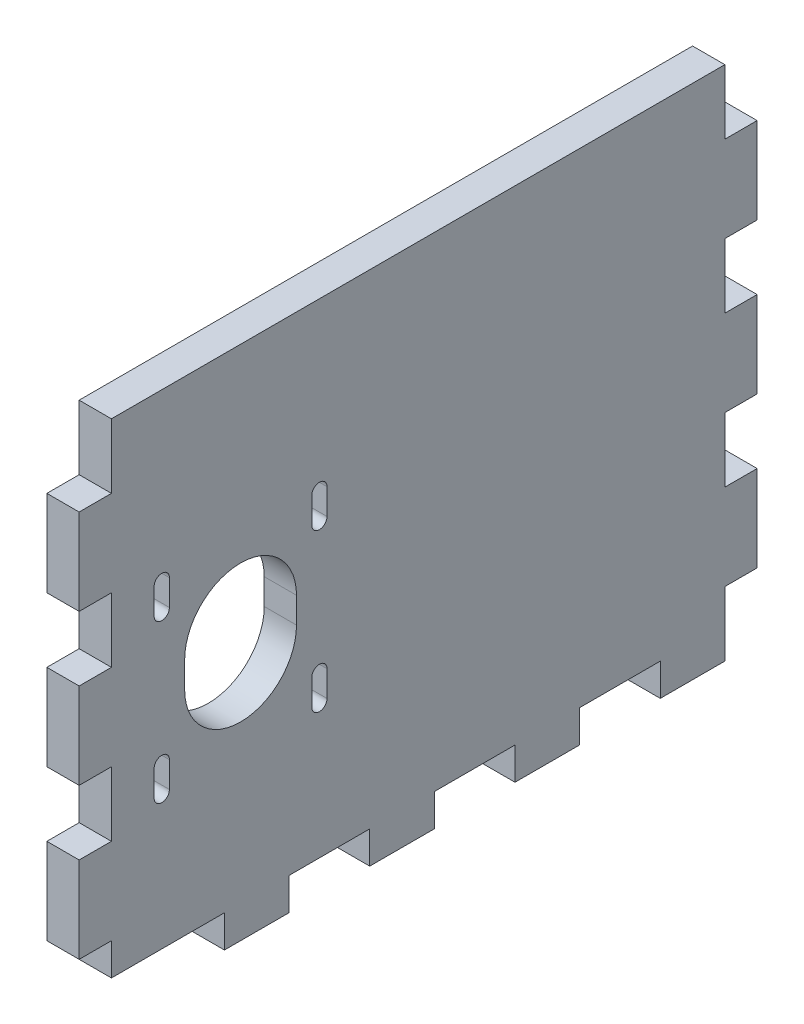
SolidWorks part; units mm, degrees
material "Acrylic (Medium-high impact)"
ref_plane "Front" through (0, 0, 0) normal (0, 0, 1) x (1, 0, 0)
ref_plane "Top" through (0, 0, 0) normal (0, 1, 0) x (1, 0, 0)
ref_plane "Right" through (0, 0, 0) normal (1, 0, 0) x (0, 0, -1)
sketch "Sketch1" plane through (0, 0, 0) normal (0, 0, 1) x (1, 0, 0)
  line L0 (0, 143.002) -> (0, -143.002) construction
  line L1 (-3.302, 133.858) -> (-3.302, -143.002)
  line L2 (-3.302, -143.002) -> (3.302, -143.002)
  line L3 (3.302, 143.002) -> (3.302, -143.002)
  line L4 (3.302, 143.002) -> (-16.256, 143.002)
  line L5 (-5.842, 136.398) -> (-16.256, 136.398)
  line L6 (-16.256, 143.002) -> (-16.256, 136.398)
  line L8 (-28.956, 155.448) -> (16.002, 155.448)
  line L9 (-28.956, 155.448) -> (-28.956, -149.352)
  line L10 (-28.956, -149.352) -> (16.002, -149.352)
  line L11 (16.002, 155.448) -> (16.002, -149.352)
  arc A0 (-3.302, 133.858) -> (-5.842, 136.398) centre (-5.842, 133.858) ccw
  point P2 (0, -143.002)
  point P11 (0, 0)
  dimension "D5" = 2.54
  dimension "D1" = 6.604
  dimension "D2" = 12.954
  dimension "D3" = 6.604
  dimension "D4" = 286.004
  dimension "D6" = 304.8
  dimension "D7" = 6.35
  dimension "D8" = 12.7
  dimension "D9" = 12.7
extrude "Boss-Extrude1" add sketch "Sketch1" along normal blind 6.35
sketch "Sketch2" plane through (16.002, 0, 0) normal (1, 0, 0) x (0, 0, -1)
  line L0 (-6.35, -149.352) -> (-6.35, 155.448) construction
  line L1 (-6.35, -47.752) -> (127, -47.752)
  line L2 (-6.35, -47.752) -> (-6.35, -149.352)
  line L3 (-6.35, -149.352) -> (127, -149.352)
  line L4 (127, -47.752) -> (127, -149.352)
  line L5 (14.4, -101.092) -> (14.4, -96.012)
  line L6 (36.4, -96.012) -> (36.4, -101.092)
  line L7 (8.4, -116.592) -> (8.4, -111.512)
  line L8 (11.4, -116.592) -> (11.4, -111.512)
  line L9 (8.4, -85.592) -> (8.4, -80.512)
  line L10 (11.4, -85.592) -> (11.4, -80.512)
  line L11 (25.4, -96.012) -> (25.4, -101.092) construction
  line L12 (42.4, -116.592) -> (42.4, -111.512)
  line L13 (39.4, -116.592) -> (39.4, -111.512)
  line L14 (39.4, -85.592) -> (39.4, -80.512)
  line L15 (42.4, -85.592) -> (42.4, -80.512)
  line L16 (0, -149.352) -> (0, 155.448) construction
  line L17 (123.825, -60.452) -> (123.825, -77.3853) construction
  line L18 (127, -47.752) -> (120.65, -47.752)
  line L19 (127, -47.752) -> (127, -60.452)
  line L20 (127, -60.452) -> (120.65, -60.452)
  line L21 (120.65, -47.752) -> (120.65, -60.452)
  line L22 (127, -107.0187) -> (120.65, -107.0187)
  line L23 (127, -107.0187) -> (127, -119.7187)
  line L24 (127, -119.7187) -> (120.65, -119.7187)
  line L25 (120.65, -107.0187) -> (120.65, -119.7187)
  line L26 (127, -136.652) -> (120.65, -136.652)
  line L27 (127, -136.652) -> (127, -149.352)
  line L28 (127, -149.352) -> (120.65, -149.352)
  line L29 (120.65, -136.652) -> (120.65, -149.352)
  line L30 (127, -77.3853) -> (120.65, -77.3853)
  line L31 (127, -77.3853) -> (127, -90.0853)
  line L32 (127, -90.0853) -> (120.65, -90.0853)
  line L33 (120.65, -77.3853) -> (120.65, -90.0853)
  line L34 (123.825, -90.0853) -> (123.825, -107.0187) construction
  line L35 (123.825, -119.7187) -> (123.825, -136.652) construction
  arc A0 (14.4, -101.092) -> (36.4, -101.092) centre (25.4, -101.092) ccw
  arc A1 (36.4, -96.012) -> (14.4, -96.012) centre (25.4, -96.012) ccw
  arc A2 (8.4, -116.592) -> (11.4, -116.592) centre (9.9, -116.592) ccw
  arc A3 (11.4, -111.512) -> (8.4, -111.512) centre (9.9, -111.512) ccw
  arc A4 (8.4, -85.592) -> (11.4, -85.592) centre (9.9, -85.592) ccw
  arc A5 (11.4, -80.512) -> (8.4, -80.512) centre (9.9, -80.512) ccw
  arc A6 (42.4, -116.592) -> (39.4, -116.592) centre (40.9, -116.592) cw
  arc A7 (39.4, -111.512) -> (42.4, -111.512) centre (40.9, -111.512) cw
  arc A8 (42.4, -85.592) -> (39.4, -85.592) centre (40.9, -85.592) cw
  arc A9 (39.4, -80.512) -> (42.4, -80.512) centre (40.9, -80.512) cw
  point P44 (25.4, -98.552)
  point P47 (-6.35, -98.552)
  line M17 (0, -149.352) -> (0, 155.448)
  line M19 (-6.35, 155.448) -> (-6.35, -149.352)
  line M20 (-6.35, -149.352) -> (0, -149.352)
  dimension "D1" = 22
  dimension "D6" = 1.5
  dimension "D10" = 1.5
  dimension "D2" = 5.08
  dimension "D3" = 5.08
  dimension "D4" = 15.5
  dimension "D5" = 15.5
  dimension "D7" = 15.5
  dimension "D8" = 15.5
  dimension "D9" = 5.08
  dimension "D11" = 25.4
  dimension "D12" = 50.8
  dimension "D13" = 101.6
  dimension "D14" = 12.7
  dimension "D15" = 6.35
extrude "Boss-Extrude2" add sketch "Sketch2" against normal blind 6.35 contours L33 L30 L4 L20 L21 L1 L3 L29 L26 L24 L25 L22 L32 A5 L10 A4 L9 A3 L8 A2 L7 A1 L6 A0 L5 L13 A7 L12 A6 L14 A9 L15 A8 M17 | L1 M19 M20 M17 region at (16.002, -98.552, -63.7235) region at (16.002, -98.552, 3.175)
sketch "Sketch3" plane through (9.652, 0, 0) normal (-1, 0, 0) x (0, 0, 1)
  line L0 (-120.65, -136.652) -> (-120.65, -149.352) construction
  line L1 (-120.65, -143.002) -> (0, -143.002)
  line L2 (-120.65, -143.002) -> (-120.65, -149.352)
  line L3 (-120.65, -149.352) -> (0, -149.352)
  line L4 (0, -143.002) -> (0, -149.352)
  dimension "D1" = 6.35
extrude "Boss-Extrude3" add sketch "Sketch3" along normal up to surface (38.608 mm away) up to face at (-28.956, 3.048, 3.175)
sketch "Sketch4" plane through (0, -149.352, 0) normal (0, -1, 0) x (1, 0, 0)
  line L0 (9.652, -22.225) -> (9.652, -34.925)
  line L1 (16.002, 6.35) -> (9.652, 6.35)
  line L2 (16.002, 6.35) -> (16.002, -6.35)
  line L3 (16.002, -6.35) -> (9.652, -6.35)
  line L4 (9.652, 6.35) -> (9.652, -6.35)
  line L5 (16.002, -22.225) -> (9.652, -22.225)
  line L6 (16.002, -22.225) -> (16.002, -34.925)
  line L7 (16.002, -34.925) -> (9.652, -34.925)
  line L8 (9.652, -50.8) -> (9.652, -63.5)
  line L9 (16.002, -50.8) -> (9.652, -50.8)
  line L10 (16.002, -50.8) -> (16.002, -63.5)
  line L11 (16.002, -63.5) -> (9.652, -63.5)
  line L12 (9.652, -79.375) -> (9.652, -92.075)
  line L13 (16.002, -79.375) -> (9.652, -79.375)
  line L14 (16.002, -79.375) -> (16.002, -92.075)
  line L15 (16.002, -92.075) -> (9.652, -92.075)
  line L16 (9.652, -107.95) -> (9.652, -120.65)
  line L17 (16.002, -107.95) -> (9.652, -107.95)
  line L18 (16.002, -107.95) -> (16.002, -120.65)
  line L19 (16.002, -120.65) -> (9.652, -120.65)
  line L36 (-6.477, 6.35) -> (-6.477, -120.65) construction
  line L37 (-28.956, 6.35) -> (16.002, 6.35) construction
  line L38 (-28.956, -120.65) -> (16.002, -120.65) construction
  line L39 (-22.606, 6.35) -> (-22.606, -120.65)
  line L40 (16.002, 6.35) -> (9.652, 6.35)
  line L41 (16.002, 6.35) -> (16.002, -120.65)
  line L42 (16.002, -120.65) -> (9.652, -120.65)
  line L43 (9.652, 6.35) -> (9.652, -120.65)
  line L44 (-28.956, -120.65) -> (-22.606, -120.65)
  line L45 (-28.956, 6.35) -> (-28.956, -120.65)
  line L46 (-28.956, 6.35) -> (-22.606, 6.35)
  line L47 (-28.956, -120.65) -> (-22.606, -120.65)
  line L48 (-28.956, -107.95) -> (-28.956, -120.65)
  line L49 (-28.956, -107.95) -> (-22.606, -107.95)
  line L50 (-22.606, -107.95) -> (-22.606, -120.65)
  line L51 (-28.956, -106.3625) -> (-22.606, -106.3625)
  line L52 (-28.956, -93.6625) -> (-28.956, -106.3625)
  line L53 (-28.956, -93.6625) -> (-22.606, -93.6625)
  line L54 (-22.606, -93.6625) -> (-22.606, -106.3625)
  line L55 (-28.956, -92.075) -> (-22.606, -92.075)
  line L56 (-28.956, -79.375) -> (-28.956, -92.075)
  line L57 (-28.956, -79.375) -> (-22.606, -79.375)
  line L58 (-22.606, -79.375) -> (-22.606, -92.075)
  line L59 (-28.956, -77.7875) -> (-22.606, -77.7875)
  line L60 (-28.956, -65.0875) -> (-28.956, -77.7875)
  line L61 (-28.956, -65.0875) -> (-22.606, -65.0875)
  line L62 (-22.606, -65.0875) -> (-22.606, -77.7875)
  line L63 (-28.956, -120.65) -> (-22.606, -120.65)
  line L64 (-28.956, -107.95) -> (-28.956, -120.65)
  line L65 (-28.956, -107.95) -> (-22.606, -107.95)
  line L66 (-22.606, -107.95) -> (-22.606, -120.65)
  line L67 (-28.956, -92.075) -> (-22.606, -92.075)
  line L68 (-28.956, -79.375) -> (-28.956, -92.075)
  line L69 (-28.956, -79.375) -> (-22.606, -79.375)
  line L70 (-22.606, -79.375) -> (-22.606, -92.075)
  line L71 (-28.956, -63.5) -> (-22.606, -63.5)
  line L72 (-28.956, -50.8) -> (-28.956, -63.5)
  line L73 (-28.956, -50.8) -> (-22.606, -50.8)
  line L74 (-22.606, -50.8) -> (-22.606, -63.5)
  line L75 (-28.956, -34.925) -> (-22.606, -34.925)
  line L76 (-28.956, -22.225) -> (-28.956, -34.925)
  line L77 (-28.956, -22.225) -> (-22.606, -22.225)
  line L78 (-22.606, 6.35) -> (-22.606, -6.35)
  line L79 (-28.956, -6.35) -> (-22.606, -6.35)
  line L80 (-28.956, 6.35) -> (-28.956, -6.35)
  line L81 (-28.956, 6.35) -> (-22.606, 6.35)
  line L82 (-22.606, -22.225) -> (-22.606, -34.925)
  line L83 (-16.129, 3.175) -> (-22.606, 3.175) construction
  line L85 (-28.956, 6.35) -> (-22.606, 6.35)
  line L86 (-28.956, 6.35) -> (-28.956, 0)
  line L87 (-28.956, 0) -> (-22.606, 0)
  line L88 (-22.606, 6.35) -> (-22.606, 0)
  line L92 (9.652, 6.35) -> (9.652, 0)
  line L93 (9.652, 6.35) -> (16.002, 6.35)
  line L94 (16.002, 6.35) -> (16.002, 0)
  line L95 (9.652, 0) -> (16.002, 0)
  line L96 (-28.956, 6.35) -> (16.002, 6.35)
  line L97 (-28.956, 6.35) -> (-28.956, 0)
  line L98 (-28.956, 0) -> (16.002, 0)
  line L99 (16.002, 6.35) -> (16.002, 0)
  line L100 (-9.652, 6.35) -> (-9.652, 0)
  line L101 (-9.652, 0) -> (-3.302, 0)
  line L102 (-3.302, 6.35) -> (-3.302, 0)
  line L103 (-9.652, 6.35) -> (-3.302, 6.35)
  line L104 (-9.779, 0) -> (-16.129, 0)
  line L105 (-9.779, 0) -> (-9.779, 6.35)
  line L106 (-9.779, 6.35) -> (-16.129, 6.35)
  line L107 (-16.129, 0) -> (-16.129, 6.35)
  line L108 (-9.779, 3.175) -> (-3.302, 3.175) construction
  line L109 (-3.302, 6.35) -> (-3.302, 0) construction
  line L111 (-28.956, 6.35) -> (16.002, 6.35)
  line L112 (-28.956, 6.35) -> (-28.956, 0)
  line L113 (-28.956, 0) -> (16.002, 0)
  line L114 (16.002, 6.35) -> (16.002, 0)
  point P23 (9.652, -118.8698)
  line M38 (16.002, -120.65) -> (16.002, 6.35)
  line M39 (16.002, 6.35) -> (-28.956, 6.35)
  dimension "D1" = 6.35
  dimension "D2" = 12.7
  dimension "D4" = 6.35
  dimension "D5" = 6.35
  dimension "D7" = 6.35
  dimension "D3" = 5
  dimension "D6" = 3
sketch "Sketch6" plane through (0, 0, 6.35) normal (0, 0, 1) x (1, 0, 0)
  line L1 (16.002, -60.452) -> (9.652, -60.452)
  line L2 (16.002, -60.452) -> (16.002, -77.3853)
  line L3 (16.002, -77.3853) -> (9.652, -77.3853)
  line L4 (9.652, -60.452) -> (9.652, -77.3853)
  line L5 (16.002, -90.0853) -> (9.652, -90.0853)
  line L6 (16.002, -90.0853) -> (16.002, -107.0187)
  line L7 (16.002, -107.0187) -> (9.652, -107.0187)
  line L8 (9.652, -90.0853) -> (9.652, -107.0187)
  line L9 (16.002, -119.7187) -> (9.652, -119.7187)
  line L10 (16.002, -119.7187) -> (16.002, -136.652)
  line L11 (16.002, -136.652) -> (9.652, -136.652)
  line L12 (9.652, -119.7187) -> (9.652, -136.652)
  line L13 (-28.956, -149.352) -> (16.002, -149.352) construction
  line L14 (16.002, -47.752) -> (9.652, -47.752)
  line L15 (16.002, -47.752) -> (16.002, -149.352)
  line L16 (16.002, -149.352) -> (9.652, -149.352)
  line L17 (9.652, -47.752) -> (9.652, -149.352)
  line M1 (16.002, -149.352) -> (16.002, 155.448)
  line M4 (-28.956, -149.352) -> (16.002, -149.352)
sketch "Sketch7" plane through (16.002, 0, 0) normal (1, 0, 0) x (0, 0, -1)
  line L1 (-6.35, 180.723) -> (327.0227, 180.723)
  line L2 (-6.35, 180.723) -> (-6.35, -143.002)
  line L3 (-6.35, -143.002) -> (327.0227, -143.002)
  line L4 (327.0227, 180.723) -> (327.0227, -143.002)
  line L5 (-6.35, -149.352) -> (-6.35, 155.448) construction
  line L6 (120.65, -143.002) -> (0, -143.002) construction
  point P10 (160.3364, -143.002)
extrude "Cut-Extrude1" [suppressed] cut sketch "Sketch7" against normal through all
extrude "Cut-Extrude2" [suppressed] cut sketch "Sketch4" against normal blind 6.35
sketch "Sketch8" plane through (0, 0, 6.35) normal (0, 0, 1) x (1, 0, 0)
  line L0 (-28.956, -149.352) -> (16.002, -149.352) construction
  line L1 (9.652, -149.352) -> (-54.2235, -149.352)
  line L2 (9.652, -149.352) -> (9.652, 165.6994)
  line L3 (9.652, 165.6994) -> (-54.2235, 165.6994)
  line L4 (-54.2235, -149.352) -> (-54.2235, 165.6994)
  line L5 (9.652, -60.452) -> (9.652, -77.3853) construction
  line L7 (16.002, -47.752) -> (9.652, -47.752)
  line L8 (16.002, -47.752) -> (16.002, 165.6994)
  line L9 (16.002, 165.6994) -> (9.652, 165.6994)
  line L10 (9.652, -47.752) -> (9.652, 165.6994)
  line M6 (16.002, 155.448) -> (-28.956, 155.448)
  line M7 (-28.956, 155.448) -> (-28.956, -149.352)
  line M8 (-28.956, -149.352) -> (16.002, -149.352)
  line M9 (-16.256, 143.002) -> (3.302, 143.002)
  line M10 (3.302, 143.002) -> (3.302, -143.002)
  line M11 (3.302, -143.002) -> (-3.302, -143.002)
  line M12 (-3.302, -143.002) -> (-3.302, 133.858)
  arc M13 (-3.302, 133.858) -> (-5.842, 136.398) centre (-5.842, 133.858) ccw
  line M14 (-5.842, 136.398) -> (-16.256, 136.398)
  line M15 (-16.256, 136.398) -> (-16.256, 143.002)
extrude "Cut-Extrude4" cut sketch "Sketch8" against normal through all and the other way through all contours L2 M8 M6 M7 M15 M9 M10 M11 M12 M13 M14 | L4 L1 L2 L3 M7 M6 | L10 L7 L8 L9 region at (-11.5135, 2.4233, 6.35) region at (-40.0771, 15.3918, 6.35)
extrude "Cut-Extrude5" cut sketch "Sketch6" against normal blind 6.35 contours L14 L17 L1 M1 | L3 L17 L5 M1 | L7 L17 L9 M1 | L11 L17 M4 M1 region at (12.827, -54.102, 6.35) region at (12.827, -83.7353, 6.35) region at (12.827, -113.3687, 6.35) region at (12.827, -143.002, 6.35)
extrude "Cut-Extrude6" cut sketch "Sketch4<3>" against normal blind 6.35 contours L15 L43 L17 M38 | L11 L43 L13 M38 | L7 L43 L9 M38 | L3 L43 L5 M38 | L4 L95 L41 M39 | L95 L43 L3 M38 region at (12.827, -149.352, -14.2875) region at (12.827, -149.352, -42.8625) region at (12.827, -149.352, -3.175) region at (12.827, -149.352, 3.175) region at (12.827, -149.352, -71.4375) region at (12.827, -149.352, -100.0125)
sketch "Sketch4<3>" plane through (0, -149.352, 0) normal (0, -1, 0) x (1, 0, 0) same geometry as "Sketch4"
